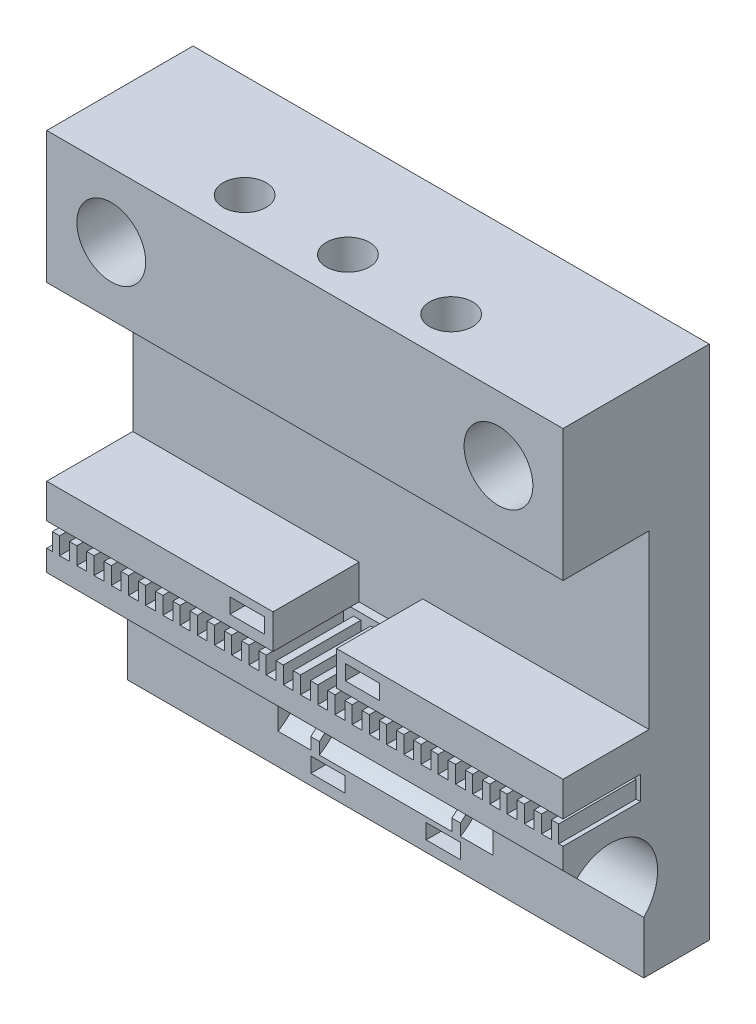
SolidWorks part; units mm, degrees
ref_plane "Front Plane" through (0, 0, 0) normal (0, 0, 1) x (1, 0, 0)
ref_plane "Top Plane" through (0, 0, 0) normal (0, 1, 0) x (1, 0, 0)
ref_plane "Right Plane" through (0, 0, 0) normal (1, 0, 0) x (0, 0, -1)
sketch "Sketch1" plane through (0, 0, 0) normal (0, 1, 0) x (1, 0, 0)
  line L1 (0, 0) -> (60, 0)
  line L2 (0, 0) -> (0, 17)
  line L3 (0, 17) -> (60, 17)
  line L4 (60, 0) -> (60, 17)
  dimension "D1" = 60
  dimension "D2" = 17
extrude "Boss-Extrude2" add sketch "Sketch1" along normal blind 60
ref_plane "Plane1" through (30, 0, 0) normal (1, 0, 0) x (0, 0, -1)
sketch "Sketch5" plane through (30, 0, 0) normal (1, 0, 0) x (0, 0, -1)
  line L0 (0, 60) -> (0, 0) construction
  line L2 (0, 0) -> (17, 0) construction
  circle A0 centre (5.5, 10) radius 7.5
  dimension "D1" = 15
  dimension "D2" = 5.5
  dimension "D3" = 10
extrude "Cut-Extrude3" cut sketch "Sketch5" against normal mid plane 25
ref_plane "Plane2" through (21.3, 0, 0) normal (1, 0, 0) x (0, 0, -1)
sketch "Sketch7" plane through (21.3, 0, 0) normal (1, 0, 0) x (0, 0, -1)
  line L0 (0, 60) -> (0, 0) construction
  line L1 (0, 0) -> (17, 0) construction
  circle A0 centre (5.5, 10) radius 6.375
  circle A1 centre (5.5, 10) radius 7.5
  dimension "D1" = 12.75
  dimension "D2" = 5.5
  dimension "D4" = 15
  dimension "D3" = 10
extrude "Boss-Extrude5" add sketch "Sketch7" along normal blind 1
ref_plane "Plane3" through (38.7, 0, 0) normal (-1, 0, 0) x (0, 0, 1)
sketch "Sketch8" plane through (38.7, 0, 0) normal (-1, 0, 0) x (0, 0, 1)
  line L0 (0, 60) -> (0, 0) construction
  line L1 (-17, 0) -> (0, 0) construction
  circle A0 centre (-5.5, 10) radius 6.375
  circle A1 centre (-5.5, 10) radius 7.5
  dimension "D1" = 12.75
  dimension "D2" = 5.5
  dimension "D3" = 10
  dimension "D4" = 15
extrude "Boss-Extrude6" add sketch "Sketch8" along normal blind 1
sketch "Sketch3" plane through (60, 0, 0) normal (1, 0, 0) x (0, 0, -1)
  line L0 (0, 0) -> (17, 0) construction
  line L1 (0, 60) -> (0, 0) construction
  line L2 (0, 15.5) -> (-6.6407, 15.5)
  line L3 (-6.6407, 15.5) -> (-6.6407, 0)
  line L4 (0, 15.5) -> (1.6109, 13.8891)
  line L5 (9.3891, 0) -> (0, 0)
  line L6 (-6.6407, 0) -> (0, 0)
  line L7 (9.3891, 6.1109) -> (9.3891, 0)
  line L9 (-5.6163, 20.7) -> (9, 20.7)
  line L10 (-5.6163, 20.7) -> (-5.6163, 17.95)
  line L11 (-5.6163, 17.95) -> (9, 17.95)
  line L12 (9, 20.7) -> (9, 17.95)
  arc A0 (9.3891, 6.1109) -> (1.6109, 13.8891) centre (5.5, 10) ccw
  dimension "D1" = 11
  dimension "D5" = 2.75
  dimension "D2" = 10
  dimension "D3" = 5.5
  dimension "D4" = 20.7
  dimension "D6" = 0
  dimension "D7" = 9
extrude "Cut-Extrude2" cut sketch "Sketch3" against normal through all
sketch "Sketch9" plane through (21.3, 0, 0) normal (1, 0, 0) x (0, 0, -1)
  line L2 (9.3891, 0) -> (17, 0) construction
  line L3 (21.7483, 3) -> (-7.6168, 3)
  line L4 (21.7483, 3) -> (21.7483, 1.25)
  line L5 (21.7483, 1.25) -> (-7.6168, 1.25)
  line L6 (-7.6168, 3) -> (-7.6168, 1.25)
  line L7 (9, 20.7) -> (0, 20.7) construction
  line L8 (-7.2884, 23.7) -> (19.5989, 23.7)
  line L9 (-7.2884, 23.7) -> (-7.2884, 21.95)
  line L10 (-7.2884, 21.95) -> (19.5989, 21.95)
  line L11 (19.5989, 23.7) -> (19.5989, 21.95)
  dimension "D1" = 1.75
  dimension "D4" = 1.25
  dimension "D2" = 1.25
  dimension "D3" = 1.75
extrude "Cut-Extrude4" cut sketch "Sketch9" along normal blind 4
sketch "Sketch10" plane through (38.7, 0, 0) normal (-1, 0, 0) x (0, 0, 1)
  line L2 (-17, 0) -> (-9.3891, 0) construction
  line L3 (-30.7394, 23.7) -> (5.8001, 23.7)
  line L4 (-30.7394, 23.7) -> (-30.7394, 21.95)
  line L5 (-30.7394, 21.95) -> (5.8001, 21.95)
  line L6 (5.8001, 23.7) -> (5.8001, 21.95)
  line L7 (-29.9886, 3) -> (8.6365, 3)
  line L8 (-29.9886, 3) -> (-29.9886, 1.25)
  line L9 (-29.9886, 1.25) -> (8.6365, 1.25)
  line L10 (8.6365, 3) -> (8.6365, 1.25)
  line L11 (-9, 20.7) -> (0, 20.7) construction
  dimension "D1" = 1.75
  dimension "D2" = 1.75
  dimension "D3" = 1.25
  dimension "D4" = 1.25
extrude "Cut-Extrude5" cut sketch "Sketch10" along normal blind 4
sketch "Sketch12" plane through (0, 0, -9) normal (0, 0, 1) x (1, 0, 0)
  line L1 (0, 17.95) -> (60, 17.95) construction
  line L2 (58.65, 17.95) -> (59.5, 17.95)
  line L3 (58.65, 17.95) -> (58.65, 19.95)
  line L4 (58.65, 19.95) -> (59.5, 19.95)
  line L5 (59.5, 17.95) -> (59.5, 19.95)
  line L6 (60, 17.95) -> (60, 20.7) construction
  line L7 (56.65, 19.95) -> (57.5, 19.95)
  line L8 (56.65, 17.95) -> (56.65, 19.95)
  line L9 (57.5, 17.95) -> (57.5, 19.95)
  line L10 (56.65, 17.95) -> (57.5, 17.95)
  line L11 (54.65, 19.95) -> (55.5, 19.95)
  line L12 (54.65, 17.95) -> (54.65, 19.95)
  line L13 (55.5, 17.95) -> (55.5, 19.95)
  line L14 (54.65, 17.95) -> (55.5, 17.95)
  line L15 (52.65, 19.95) -> (53.5, 19.95)
  line L16 (52.65, 17.95) -> (52.65, 19.95)
  line L17 (53.5, 17.95) -> (53.5, 19.95)
  line L18 (52.65, 17.95) -> (53.5, 17.95)
  line L19 (50.65, 19.95) -> (51.5, 19.95)
  line L20 (50.65, 17.95) -> (50.65, 19.95)
  line L21 (51.5, 17.95) -> (51.5, 19.95)
  line L22 (50.65, 17.95) -> (51.5, 17.95)
  line L23 (48.65, 19.95) -> (49.5, 19.95)
  line L24 (48.65, 17.95) -> (48.65, 19.95)
  line L25 (49.5, 17.95) -> (49.5, 19.95)
  line L26 (48.65, 17.95) -> (49.5, 17.95)
  line L27 (46.65, 19.95) -> (47.5, 19.95)
  line L28 (46.65, 17.95) -> (46.65, 19.95)
  line L29 (47.5, 17.95) -> (47.5, 19.95)
  line L30 (46.65, 17.95) -> (47.5, 17.95)
  line L31 (44.65, 19.95) -> (45.5, 19.95)
  line L32 (44.65, 17.95) -> (44.65, 19.95)
  line L33 (45.5, 17.95) -> (45.5, 19.95)
  line L34 (44.65, 17.95) -> (45.5, 17.95)
  line L35 (42.65, 19.95) -> (43.5, 19.95)
  line L36 (42.65, 17.95) -> (42.65, 19.95)
  line L37 (43.5, 17.95) -> (43.5, 19.95)
  line L38 (42.65, 17.95) -> (43.5, 17.95)
  line L39 (40.65, 19.95) -> (41.5, 19.95)
  line L40 (40.65, 17.95) -> (40.65, 19.95)
  line L41 (41.5, 17.95) -> (41.5, 19.95)
  line L42 (40.65, 17.95) -> (41.5, 17.95)
  line L43 (38.65, 19.95) -> (39.5, 19.95)
  line L44 (38.65, 17.95) -> (38.65, 19.95)
  line L45 (39.5, 17.95) -> (39.5, 19.95)
  line L46 (38.65, 17.95) -> (39.5, 17.95)
  line L47 (36.65, 19.95) -> (37.5, 19.95)
  line L48 (36.65, 17.95) -> (36.65, 19.95)
  line L49 (37.5, 17.95) -> (37.5, 19.95)
  line L50 (36.65, 17.95) -> (37.5, 17.95)
  line L51 (34.65, 19.95) -> (35.5, 19.95)
  line L52 (34.65, 17.95) -> (34.65, 19.95)
  line L53 (35.5, 17.95) -> (35.5, 19.95)
  line L54 (34.65, 17.95) -> (35.5, 17.95)
  line L55 (32.65, 19.95) -> (33.5, 19.95)
  line L56 (32.65, 17.95) -> (32.65, 19.95)
  line L57 (33.5, 17.95) -> (33.5, 19.95)
  line L58 (32.65, 17.95) -> (33.5, 17.95)
  line L59 (30.65, 19.95) -> (31.5, 19.95)
  line L60 (30.65, 17.95) -> (30.65, 19.95)
  line L61 (31.5, 17.95) -> (31.5, 19.95)
  line L62 (30.65, 17.95) -> (31.5, 17.95)
  line L63 (28.65, 19.95) -> (29.5, 19.95)
  line L64 (28.65, 17.95) -> (28.65, 19.95)
  line L65 (29.5, 17.95) -> (29.5, 19.95)
  line L66 (28.65, 17.95) -> (29.5, 17.95)
  line L67 (26.65, 19.95) -> (27.5, 19.95)
  line L68 (26.65, 17.95) -> (26.65, 19.95)
  line L69 (27.5, 17.95) -> (27.5, 19.95)
  line L70 (26.65, 17.95) -> (27.5, 17.95)
  line L71 (24.65, 19.95) -> (25.5, 19.95)
  line L72 (24.65, 17.95) -> (24.65, 19.95)
  line L73 (25.5, 17.95) -> (25.5, 19.95)
  line L74 (24.65, 17.95) -> (25.5, 17.95)
  line L75 (22.65, 19.95) -> (23.5, 19.95)
  line L76 (22.65, 17.95) -> (22.65, 19.95)
  line L77 (23.5, 17.95) -> (23.5, 19.95)
  line L78 (22.65, 17.95) -> (23.5, 17.95)
  line L79 (20.65, 19.95) -> (21.5, 19.95)
  line L80 (20.65, 17.95) -> (20.65, 19.95)
  line L81 (21.5, 17.95) -> (21.5, 19.95)
  line L82 (20.65, 17.95) -> (21.5, 17.95)
  line L83 (18.65, 19.95) -> (19.5, 19.95)
  line L84 (18.65, 17.95) -> (18.65, 19.95)
  line L85 (19.5, 17.95) -> (19.5, 19.95)
  line L86 (18.65, 17.95) -> (19.5, 17.95)
  line L87 (16.65, 19.95) -> (17.5, 19.95)
  line L88 (16.65, 17.95) -> (16.65, 19.95)
  line L89 (17.5, 17.95) -> (17.5, 19.95)
  line L90 (16.65, 17.95) -> (17.5, 17.95)
  line L91 (14.65, 19.95) -> (15.5, 19.95)
  line L92 (14.65, 17.95) -> (14.65, 19.95)
  line L93 (15.5, 17.95) -> (15.5, 19.95)
  line L94 (14.65, 17.95) -> (15.5, 17.95)
  line L95 (12.65, 19.95) -> (13.5, 19.95)
  line L96 (12.65, 17.95) -> (12.65, 19.95)
  line L97 (13.5, 17.95) -> (13.5, 19.95)
  line L98 (12.65, 17.95) -> (13.5, 17.95)
  line L99 (10.65, 19.95) -> (11.5, 19.95)
  line L100 (10.65, 17.95) -> (10.65, 19.95)
  line L101 (11.5, 17.95) -> (11.5, 19.95)
  line L102 (10.65, 17.95) -> (11.5, 17.95)
  line L103 (8.65, 19.95) -> (9.5, 19.95)
  line L104 (8.65, 17.95) -> (8.65, 19.95)
  line L105 (9.5, 17.95) -> (9.5, 19.95)
  line L106 (8.65, 17.95) -> (9.5, 17.95)
  line L107 (6.65, 19.95) -> (7.5, 19.95)
  line L108 (6.65, 17.95) -> (6.65, 19.95)
  line L109 (7.5, 17.95) -> (7.5, 19.95)
  line L110 (6.65, 17.95) -> (7.5, 17.95)
  line L111 (4.65, 19.95) -> (5.5, 19.95)
  line L112 (4.65, 17.95) -> (4.65, 19.95)
  line L113 (5.5, 17.95) -> (5.5, 19.95)
  line L114 (4.65, 17.95) -> (5.5, 17.95)
  line L115 (2.65, 19.95) -> (3.5, 19.95)
  line L116 (2.65, 17.95) -> (2.65, 19.95)
  line L117 (3.5, 17.95) -> (3.5, 19.95)
  line L118 (2.65, 17.95) -> (3.5, 17.95)
  line L119 (0.65, 19.95) -> (1.5, 19.95)
  line L120 (0.65, 17.95) -> (0.65, 19.95)
  line L121 (1.5, 17.95) -> (1.5, 19.95)
  line L122 (0.65, 17.95) -> (1.5, 17.95)
  dimension "D1" = 0.85
  dimension "D2" = 2
  dimension "D3" = 0
  dimension "D4" = 0.5
  dimension "D5" = 30
extrude "Boss-Extrude7" add sketch "Sketch12" along normal up to surface (9 mm away) up to face at (30, 16.725, 0)
sketch "Sketch13" plane through (0, 0, 0) normal (0, 0, 1) x (1, 0, 0)
  line L0 (33.7, 24.7) -> (33.7, 20.7)
  line L1 (33.7, 20.7) -> (26.3, 20.7)
  line L2 (26.3, 20.7) -> (26.3, 24.7)
  line L3 (26.3, 24.7) -> (-1.3909, 24.7)
  line L4 (-1.3909, 24.7) -> (-1.3909, 44.7)
  line L5 (-1.3909, 44.7) -> (62.5919, 44.7)
  line L6 (62.5919, 44.7) -> (62.5919, 24.7)
  line L7 (62.5919, 24.7) -> (33.7, 24.7)
  line L8 (34.7, 21.95) -> (34.7, 23.7) construction
  line L9 (25.3, 23.7) -> (25.3, 21.95) construction
  line L10 (0, 20.7) -> (60, 20.7) construction
  line L11 (25.3, 23.7) -> (21.3, 23.7) construction
  line L12 (38.7, 23.7) -> (34.7, 23.7) construction
  dimension "D1" = 1
  dimension "D2" = 1
  dimension "D3" = 0
  dimension "D4" = 1
  dimension "D5" = 1
  dimension "D6" = 20
extrude "Cut-Extrude6" cut sketch "Sketch13" against normal blind 10
sketch "Sketch14" plane through (0, 0, 0) normal (0, 0, 1) x (1, 0, 0)
  line L0 (0, 60) -> (60, 60) construction
  line L1 (0, 60) -> (0, 44.7) construction
  circle A0 centre (7.5, 52.5) radius 4
  circle A1 centre (52.5, 52.5) radius 4
  dimension "D1" = 8
  dimension "D2" = 7.5
  dimension "D3" = 8
  dimension "D4" = 7.5
  dimension "D5" = 45
  dimension "D6" = 7.5
extrude "Cut-Extrude7" cut sketch "Sketch14" against normal blind 15
sketch "Sketch15" plane through (0, 44.7, 0) normal (0, -1, 0) x (1, 0, 0)
  line L0 (60, 0) -> (0, 0) construction
  line L2 (60, 0) -> (60, -10) construction
  circle A0 centre (30, -5) radius 2.5
  circle A1 centre (18, -5) radius 2.5
  circle A2 centre (42, -5) radius 2.5
  dimension "D1" = 5
  dimension "D3" = 30
  dimension "D4" = 5
  dimension "D6" = 5
  dimension "D2" = 5
  dimension "D5" = 12
  dimension "D7" = 12
  dimension "D8" = 0
extrude "Cut-Extrude8" cut sketch "Sketch15" against normal up to surface (15.3 mm away) up to face at (30, 60, -8.5)
